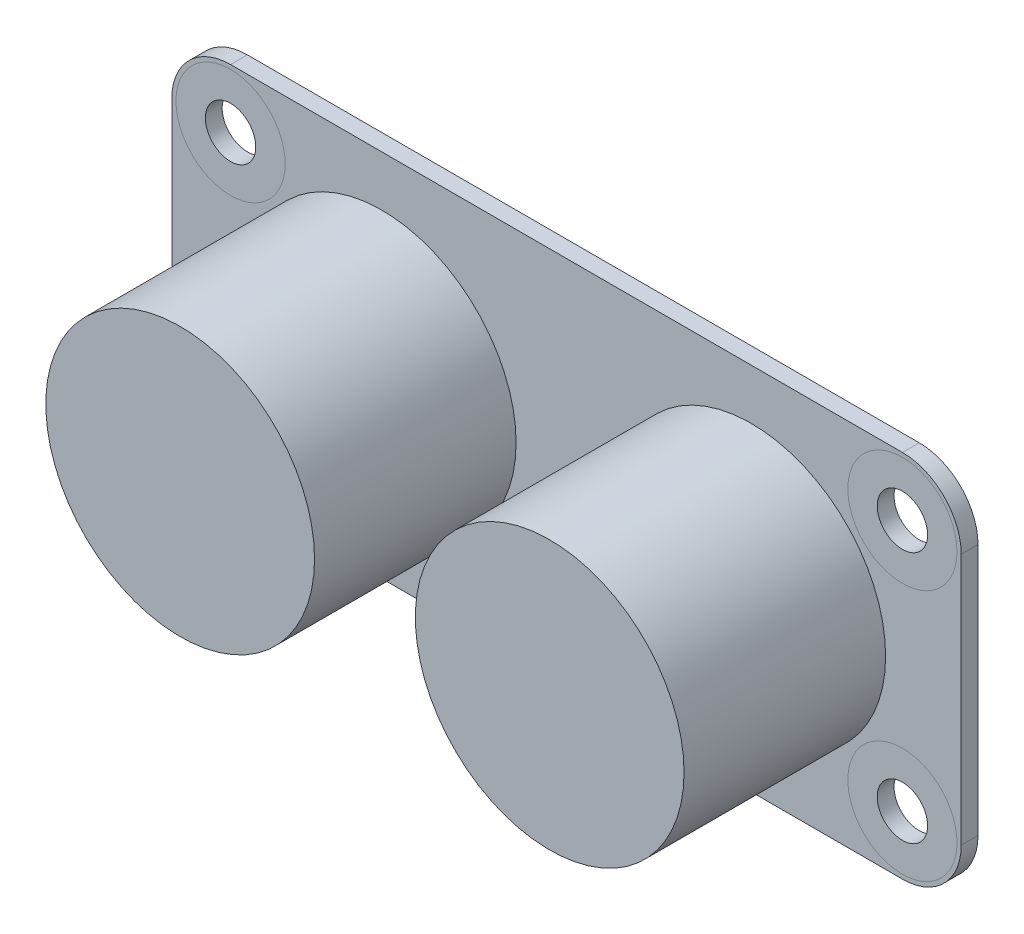
SolidWorks part; units mm, degrees
ref_plane "Front Plane" through (0, 0, 0) normal (0, 0, 1) x (1, 0, 0)
ref_plane "Top Plane" through (0, 0, 0) normal (0, 1, 0) x (1, 0, 0)
ref_plane "Right Plane" through (0, 0, 0) normal (1, 0, 0) x (0, 0, -1)
sketch "Sketch1" plane through (0, 0, 0) normal (0, 0, 1) x (1, 0, 0)
  line L0 (-11, 0) -> (11, 0) construction
  line L1 (23.5, -11) -> (-23.5, -11)
  line L2 (23.5, -11) -> (23.5, 11)
  line L3 (23.5, 11) -> (-23.5, 11)
  line L4 (-23.5, -11) -> (-23.5, 11)
  line L5 (23.5, -11) -> (-23.5, 11) construction
  line L6 (23.5, 11) -> (-23.5, -11) construction
  circle A0 centre (11, 0) radius 8
  circle A1 centre (-11, 0) radius 8
  point P0 (0, 0)
  point P8 (0, 0)
  dimension "D3" = 16
  dimension "D4" = 22
  dimension "D1" = 47
  dimension "D2" = 22
extrude "Boss-Extrude1" add sketch "Sketch1" along normal blind 1 contours A1 | A0 | L4 L1 L2 L3 A1 A0 region at (0, 0, 0) region at (11, 0, 0) region at (-11, 0, 0)
extrude "Boss-Extrude2" add sketch "Sketch1<3>" along normal blind 12 from surface contours A0 | A1 starting at face at (0, 0, 1)
sketch "Sketch1<3>" plane through (0, 0, 0) normal (0, 0, 1) x (1, 0, 0) same geometry as "Sketch1"
sketch "Sketch2" plane through (0, 0, 0) normal (0, 0, 1) x (1, 0, 0)
  line L4 (23.5, 11) -> (-23.5, -11) construction
  line L5 (20, -7.5) -> (-20, -7.5) construction
  line L6 (20, -7.5) -> (20, 7.5) construction
  line L7 (20, 7.5) -> (-20, 7.5) construction
  line L8 (-20, -7.5) -> (-20, 7.5) construction
  line L9 (20, -7.5) -> (-20, 7.5) construction
  line L10 (20, 7.5) -> (-20, -7.5) construction
  line L12 (-23.5, -11) -> (-23.5, 11) construction
  circle A0 centre (-20, 7.5) radius 1.5
  circle A1 centre (-20, 7.5) radius 3.25
  circle A2 centre (20, 7.5) radius 3.25
  circle A3 centre (20, 7.5) radius 1.5
  circle A4 centre (20, -7.5) radius 3.25
  circle A5 centre (20, -7.5) radius 1.5
  circle A6 centre (-20, -7.5) radius 1.5
  circle A7 centre (-20, -7.5) radius 3.25
  point P2 (0, 0)
  dimension "D3" = 3
  dimension "D4" = 6.5
  dimension "D1" = 15
  dimension "D2" = 3.5
extrude "Cut-Extrude1" cut sketch "Sketch2<3>" along normal up to surface (1 mm away) contours A3 | A0 | A6 | A5 region at (-20, 7.5, 0) region at (20, 7.5, 0) region at (20, -7.5, 0) region at (-20, -7.5, 0) up to face at (-3, 0, 1)
sketch "Sketch2<3>" plane through (0, 0, 0) normal (0, 0, 1) x (1, 0, 0) same geometry as "Sketch2"
split line "Split Line1"
fillet "Fillet1" radius 3.5 4 edges at (-23.5, -11, 0.5) (23.5, -11, 0.5) (-23.5, 11, 0.5) (23.5, 11, 0.5)
sketch "Sketch3" plane through (0, 0, 0) normal (0, 0, -1) x (-1, 0, 0)
  line L0 (0, 0) -> (0, -8) construction
  line L1 (5, -11) -> (-5, -11)
  line L2 (5, -11) -> (5, -5)
  line L3 (5, -5) -> (-5, -5)
  line L4 (-5, -11) -> (-5, -5)
  line L5 (5, -11) -> (-5, -5) construction
  line L6 (5, -5) -> (-5, -11) construction
  line L7 (-20, -11) -> (20, -11) construction
  point P0 (0, -8)
  dimension "D1" = 10
  dimension "D2" = 6
extrude "Boss-Extrude3" add sketch "Sketch3" along normal blind 6
sketch "Sketch4" plane through (0, 0, -6) normal (0, 0, -1) x (-1, 0, 0)
  line L0 (5, -5) -> (-5, -5) construction
  line L1 (4, -10) -> (-4, -10)
  line L2 (4, -10) -> (4, -5)
  line L3 (4, -5) -> (-4, -5)
  line L4 (-4, -10) -> (-4, -5)
  line L5 (4, -10) -> (-4, -5) construction
  line L6 (4, -5) -> (-4, -10) construction
  point P0 (0, -7.5)
  dimension "D1" = 8
  dimension "D2" = 5
extrude "Boss-Extrude4" add sketch "Sketch4" along normal blind 2.5
sketch "Sketch5" plane through (0, 0, -8.5) normal (0, 0, -1) x (-1, 0, 0)
  line L0 (-2, -8) -> (2, -8) construction
  line L1 (0, -5) -> (0, -11) construction
  line L2 (4, -5) -> (-4, -5) construction
  line L3 (-5, -11) -> (5, -11) construction
  circle A0 centre (-2, -8) radius 0.75
  circle A1 centre (0, -8) radius 0.75
  circle A2 centre (2, -8) radius 0.75
  dimension "D2" = 1.5
  dimension "D1" = 4
extrude "Boss-Extrude5" add sketch "Sketch5" along normal blind 3
